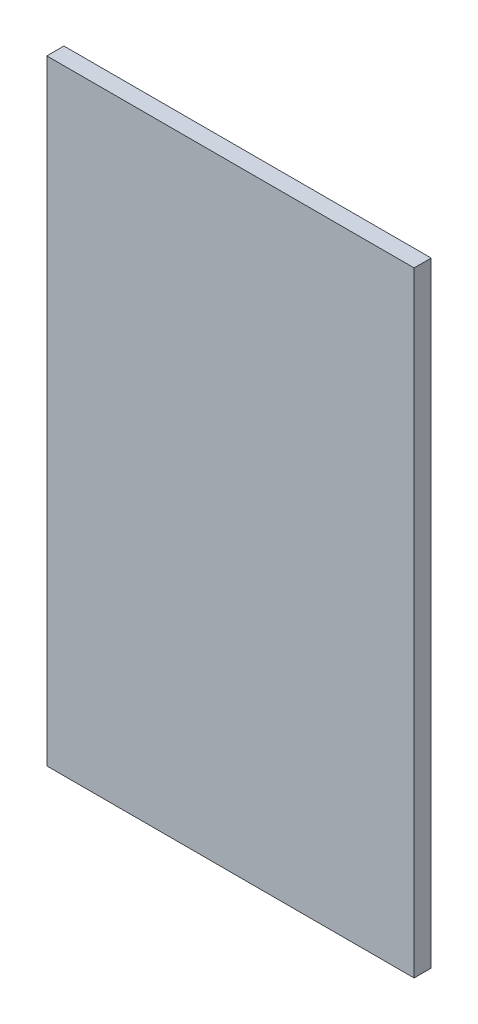
SolidWorks part; units mm, degrees
material "Acrylic (Medium-high impact)"
ref_plane "Front Plane" through (0, 0, 0) normal (0, 0, 1) x (1, 0, 0)
ref_plane "Top Plane" through (0, 0, 0) normal (0, 1, 0) x (1, 0, 0)
ref_plane "Right Plane" through (0, 0, 0) normal (1, 0, 0) x (0, 0, -1)
sketch "Sketch1" plane through (0, 0, 0) normal (0, 1, 0) x (1, 0, 0)
  line L1 (-71.4375, -5.5563) -> (65.0875, -5.5562)
  line L2 (-71.4375, -5.5563) -> (-71.4375, 0.7938)
  line L3 (-71.4375, 0.7938) -> (65.0875, 0.7938)
  line L4 (65.0875, -5.5562) -> (65.0875, 0.7938)
  line L5 (-71.4375, -5.5563) -> (65.0875, 0.7938) construction
  line L6 (-71.4375, 0.7938) -> (65.0875, -5.5562) construction
  point P0 (-3.175, -2.3813)
  dimension "D1" = 136.525
  dimension "D2" = 6.35
extrude "Boss-Extrude1" add sketch "Sketch1" along normal blind 114.3 and the other way blind 114.3
